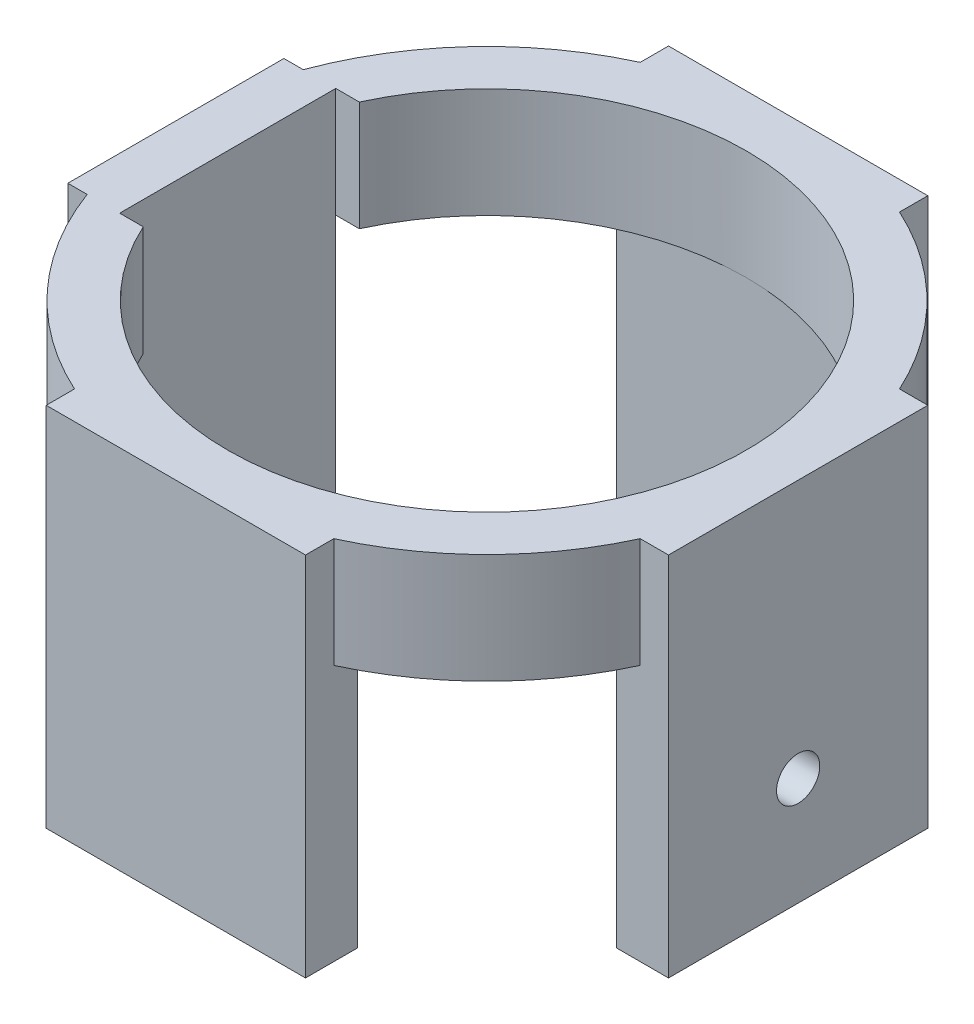
SolidWorks part; units mm, degrees
ref_plane "Front Plane" through (0, 0, 0) normal (0, 0, 1) x (1, 0, 0)
ref_plane "Top Plane" through (0, 0, 0) normal (0, 1, 0) x (1, 0, 0)
ref_plane "Right Plane" through (0, 0, 0) normal (1, 0, 0) x (0, 0, -1)
sketch "Sketch1" plane through (0, 0, 0) normal (0, 1, 0) x (1, 0, 0)
  circle A0 centre (0, 0) radius 72
  circle A1 centre (0, 0) radius 60
  dimension "D1" = 12
  dimension "D2" = 120
extrude "Boss-Extrude1" add sketch "Sketch1" against normal blind 25.4
ref_plane "Plane2" through (-60, 0, 0) normal (1, 0, 0) x (0, 0, -1)
sketch "Sketch6" plane through (-60, 0, 0) normal (1, 0, 0) x (0, 0, -1)
  line L0 (0, 0) -> (0, -59.7705)
  line L1 (72, 0) -> (-72, 0) construction
  dimension "D1" = 59.7705
sketch "Sketch7" plane through (-60, 0, 0) normal (1, 0, 0) x (0, 0, -1)
  line L0 (-60, -25.4) -> (60, -25.4) construction
  line L1 (-60, -25.4) -> (60, -25.4) construction
  line L2 (0, -81.8336) -> (0, -59.7705) construction
  line L3 (-25, -25.4) -> (25, -25.4) construction
  line L4 (-25, -25.4) -> (-25, -81.8336)
  line L5 (-25, -81.8336) -> (25, -81.8336)
  line L6 (25, -25.4) -> (25, -81.8336)
  line L7 (60, 0) -> (-60, 0) construction
  line L8 (60, 0) -> (-60, 0) construction
  line L10 (-25, -25.4) -> (25, -25.4) construction
  line L11 (-25, -25.4) -> (-25, 0)
  line L12 (-25, 0) -> (25, 0)
  line L13 (25, -25.4) -> (25, 0)
  point P2 (0, -59.7705)
  dimension "D1" = 22.0631
  dimension "D2" = 50
ref_plane "Plane3" through (-72, 0, 0) normal (-1, 0, 0) x (0, 0, 1)
extrude "Boss-Extrude4" add sketch "Sketch7" against normal up to surface (12 mm away) contours L6 L5 L4 L11 L12 L13 up to plane "Plane3"
sketch "Sketch15" plane through (0, -25.4, 0) normal (0, -1, 0) x (1, 0, 0)
  line L0 (-60, 25) -> (-54.5436, 25)
  line L2 (-60, -25) -> (-54.5436, -25)
  line L3 (-60, -25) -> (-60, 0) construction
  line L4 (-60, 0) -> (-60, 25) construction
  line L5 (-60, -25) -> (-60, 0)
  line L6 (-60, 0) -> (-60, 25)
  line L7 (-54.5436, 25) -> (-54.5436, -25)
  circle A1 centre (0, 0) radius 60 construction
extrude "Cut-Extrude1" cut sketch "Sketch15" against normal up to surface (25.4 mm away) up to face at (0, 0, 60)
ref_axis "Axis2" through (-60.6006, -59.7705, 0) along (1, 0, 0)
ref_plane "Plane4" through (60, 0, 0) normal (-1, 0, 0) x (0, 0, 1)
ref_plane "Plane5" through (72, 0, 0) normal (1, 0, 0) x (0, 0, -1)
sketch "Sketch8" plane through (60, 0, 0) normal (-1, 0, 0) x (0, 0, 1)
  line L0 (0, 0) -> (0, -84.7705) construction
  line L2 (-30, 0) -> (30, 0)
  line L3 (-30, 0) -> (-30, -84.7705)
  line L4 (-30, -84.7705) -> (30, -84.7705)
  line L5 (30, 0) -> (30, -84.7705)
  line L6 (60, 0) -> (-60, 0) construction
  line L7 (60, 0) -> (-60, 0) construction
  point P0 (0, -59.7705)
  dimension "D1" = 25
  dimension "D2" = 60
extrude "Boss-Extrude5" add sketch "Sketch8" against normal up to surface (12 mm away) contours L3 L4 L5 L2 up to plane "Plane5"
pattern_circular "CirPattern4" count 2 every 90 about axis through (0, -25.4, 0) along (0, 1, 0) other way count 2 of face at (65.8174, -36.7235, 30) of face at (60, -49.1482, 0) of face at (66, -84.7705, 0) of face at (72, -42.3853, 0) of face at (65.8174, -36.7235, -30)
sketch "Sketch10" plane through (60, 0, 0) normal (-1, 0, 0) x (0, 0, 1)
  point P0 (0, -59.7705)
hole_wizard "M8 Clearance Hole1" positions "Sketch12" profile "Sketch13" hole size "M8" standard "ANSI Metric" end condition up to next
sketch "Sketch12" plane through (60, 0, 0) normal (-1, 0, 0) x (0, 0, 1)
  point P0 (0, -59.7705)
sketch "Sketch13" plane through (60, -59.7705, 0) normal (0, 1, 0) x (0, 0, 1)
  line L0 (0, 0) -> (0, 12)
  line L1 (0, 12) -> (5, 12)
  line L2 (5, 12) -> (5, 0)
  line L5 (5, 0) -> (0, 0)
  line L11 (0, -6.35) -> (0, 107.95) construction
  dimension "Thru Hole Dia." = 10
  dimension "Thru Hole Depth" = 12
ref_axis "Axis3" through (0, -21.2693, 0) along (0, 1, 0)
ref_point "Point1"
